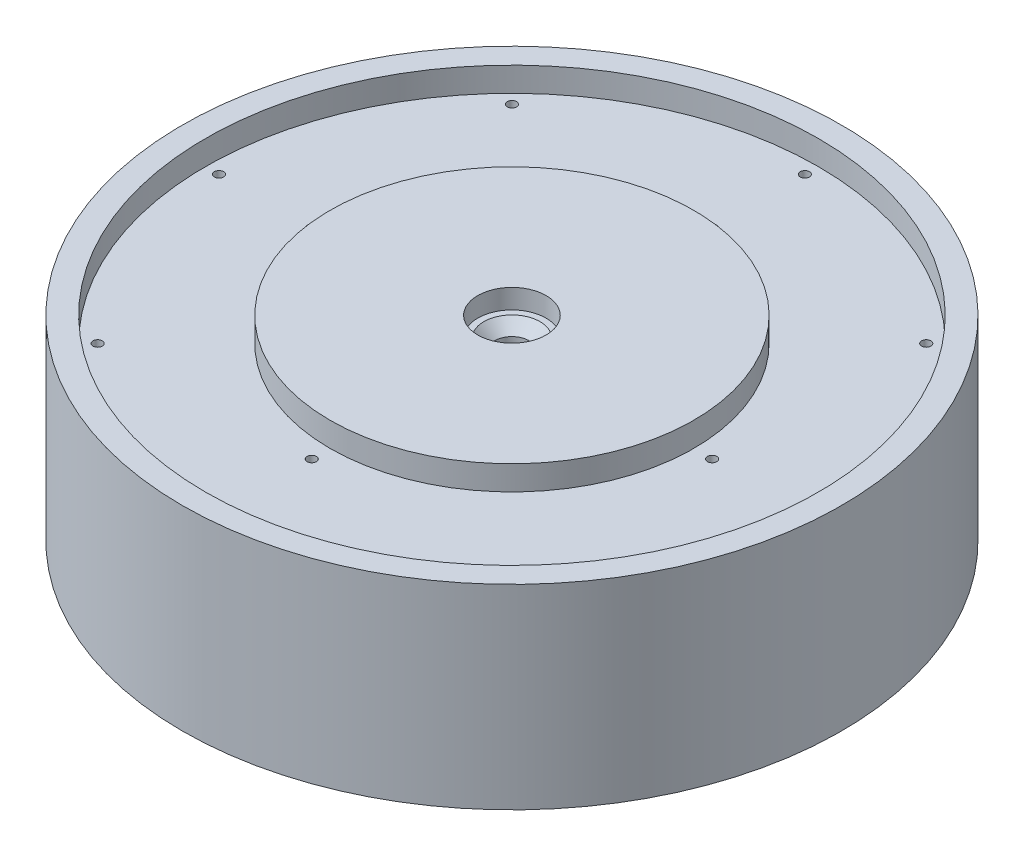
SolidWorks part; units mm, degrees
material "Ст 3 ГОСТ 380-88"
ref_plane "Front Plane" through (0, 0, 0) normal (0, 0, 1) x (1, 0, 0)
ref_plane "Top Plane" through (0, 0, 0) normal (0, 1, 0) x (1, 0, 0)
ref_plane "Right Plane" through (0, 0, 0) normal (1, 0, 0) x (0, 0, -1)
sketch "Sketch1" plane through (0, 0, 0) normal (0, 1, 0) x (1, 0, 0)
  line L0 (0, 139.3128) -> (0, -172.1696) construction
  line L1 (-149.827, 0) -> (182.6838, 0) construction
  line L2 (0, 0) -> (0, 127.2955) construction
  circle A0 centre (0, 0) radius 135
  circle A1 centre (0, 0) radius 37.5 construction
  circle A2 centre (0, 37.5) radius 1.75 construction
  circle A3 centre (26.5165, 26.5165) radius 1.75 construction
  circle A4 centre (37.5, 0) radius 1.75 construction
  circle A5 centre (26.5165, -26.5165) radius 1.75 construction
  circle A6 centre (0, -37.5) radius 1.75 construction
  circle A7 centre (-26.5165, -26.5165) radius 1.75 construction
  circle A8 centre (-37.5, 0) radius 1.75 construction
  circle A9 centre (-26.5165, 26.5165) radius 1.75 construction
  circle A10 centre (0, 0) radius 7
  circle A11 centre (0, 120) radius 1.9
  circle A12 centre (0, 0) radius 120 construction
  circle A13 centre (84.8528, 84.8528) radius 1.9
  circle A14 centre (120, 0) radius 1.9
  circle A15 centre (84.8528, -84.8528) radius 1.9
  circle A16 centre (0, -120) radius 1.9
  circle A17 centre (-84.8528, -84.8528) radius 1.9
  circle A18 centre (-120, 0) radius 1.9
  circle A19 centre (-84.8528, 84.8528) radius 1.9
  circle A20 centre (0, 0) radius 82 construction
  circle A37 centre (0, 82) radius 1.9
  circle A38 centre (82, 0) radius 1.9
  circle A39 centre (0, -82) radius 1.9
  circle A40 centre (-82, 0) radius 1.9
  point P26 (0, 0)
  point P46 (0, 0)
  point P129 (0, 0)
  dimension "D1" = 270
  dimension "D2" = 75
  dimension "D3" = 3.5
  dimension "D4" = 14
  dimension "D6" = 3.8
  dimension "D7" = 240
  dimension "D9" = 164
  dimension "D11" = 3.8
  dimension "D5" = 8
  dimension "D8" = 8
  dimension "D12" = 4
extrude "Boss-Extrude1" add sketch "Sketch1" along normal mid plane 80 contours A0 | A10
sketch "Sketch2" plane through (0, 40, 0) normal (0, 1, 0) x (1, 0, 0)
  circle A0 centre (0, 0) radius 14
  dimension "D1" = 28
extrude "Cut-Extrude1" cut sketch "Sketch2" against normal blind 8 contours A0
extrude "Cut-Extrude2" cut sketch "Sketch2<3>" along normal blind 8 from surface starting at face at (0, -40, 135)
sketch "Sketch2<3>" plane through (0, 40, 0) normal (0, 1, 0) x (1, 0, 0) same geometry as "Sketch2"
chamfer "Chamfer1" distance 4.5 angle 45 2 edges at (0, 32, 7) (0, -32, 7)
sketch "Sketch3" plane through (0, 0, 0) normal (1, 0, 0) x (0, 0, -1)
  line L0 (0, 58.9252) -> (0, -51.8708) construction
  line L1 (-125.5, 40) -> (-125.5, 30)
  line L2 (135, 40) -> (-135, 40) construction
  line L3 (-125.5, 30) -> (-74.5, 30)
  line L4 (-74.5, 30) -> (-74.5, 40)
  line L5 (0, 0) -> (-139.3499, 0) construction
  line L6 (-125.5, 40) -> (-74.5, 40)
  line L7 (-125.5, -40) -> (-74.5, -40)
  line L8 (-74.5, -30) -> (-74.5, -40)
  line L9 (-125.5, -30) -> (-74.5, -30)
  line L10 (-125.5, -40) -> (-125.5, -30)
  line L11 (-135, 40) -> (-135, -40) construction
  dimension "D1" = 9.5
  dimension "D2" = 10
  dimension "D3" = 51
revolve "Cut-Revolve1" cut sketch "Sketch3" angle 360 about L0
extrude "Cut-Extrude3" cut sketch "Sketch1<3>" against normal blind 20 from surface contours A37 | A38 | A39 | A40 | A11 | A13 | A14 | A15 | A16 | A17 | A18 | A19 starting at face at (0, 30, 74.5)
sketch "Sketch1<3>" plane through (0, 0, 0) normal (0, 1, 0) x (1, 0, 0) same geometry as "Sketch1"
mirror "Mirror1" about plane through (0, 0, 0) normal (0, 1, 0) of "Cut-Extrude3"
